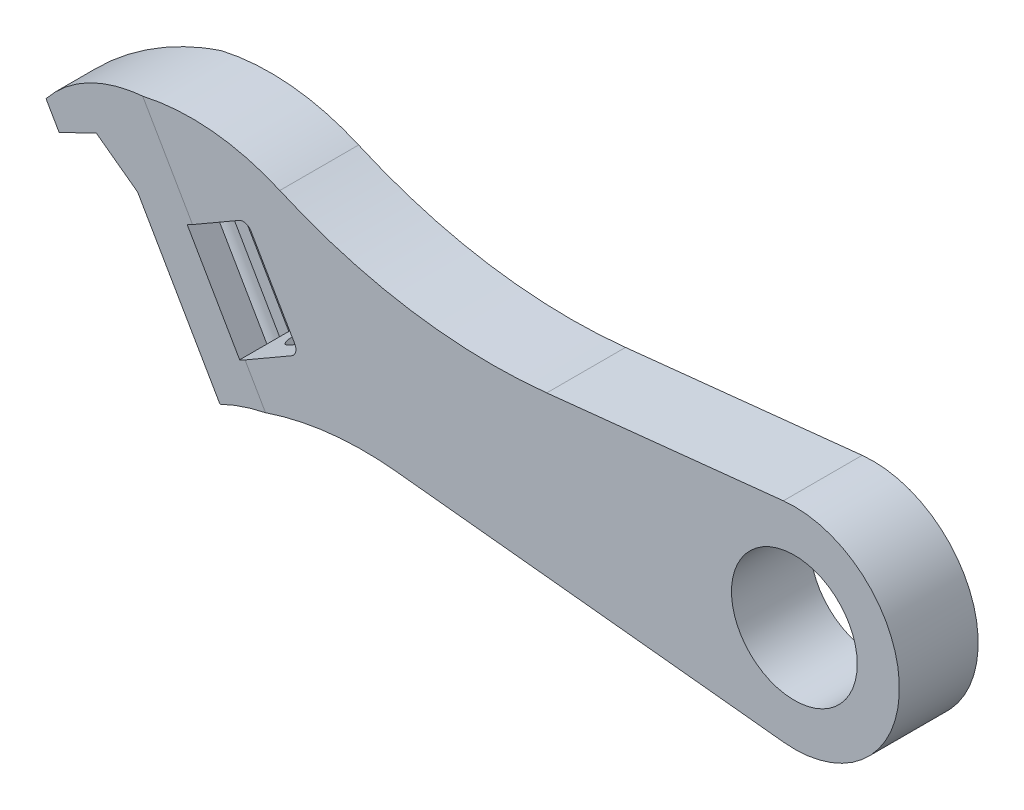
SolidWorks part; units mm, degrees
ref_plane "Front Plane" through (0, 0, 0) normal (0, 0, 1) x (1, 0, 0)
ref_plane "Top Plane" through (0, 0, 0) normal (0, 1, 0) x (1, 0, 0)
ref_plane "Right Plane" through (0, 0, 0) normal (1, 0, 0) x (0, 0, -1)
sketch "Sketch1" plane through (0, 0, 0) normal (0, 0, 1) x (1, 0, 0)
  line L0 (-1.2543, 11.9343) -> (-28.2897, 9.0927)
  line L1 (-1.2543, -11.9343) -> (-45.5473, -7.2789)
  line L2 (0, 0) -> (-132.4095, 0) construction
  line L3 (-88, 7.1064) -> (-86.5, 4.5083)
  line L4 (-86.5, 4.5083) -> (-81.3038, 7.5083)
  line L5 (-81.3038, 7.5083) -> (-76.1077, 4.5083)
  line L6 (-76.1077, 4.5083) -> (-66.7058, -11.7763)
  line L7 (-69.5096, 5.0801) -> (-63.5096, -5.3122)
  line L8 (-63.5096, -5.3122) -> (-57.4474, -1.8122)
  line L9 (-57.0814, -0.4461) -> (-62.0814, 8.2141)
  line L10 (-63.4474, 8.5801) -> (-69.5096, 5.0801)
  line L11 (-95.5176, 16) -> (-42.2419, 16) construction
  line L12 (0, -12) -> (24.4473, -12) construction
  line L13 (-66.7058, -11.7763) -> (-98.6065, -30.1942) construction
  circle A0 centre (0, 0) radius 7.1846
  arc A1 (-1.2543, 11.9343) -> (-1.2543, -11.9343) centre (0, 0) cw
  arc A2 (-45.5473, -7.2789) -> (-66.7058, -11.7763) centre (-49.2058, -42.0872) ccw
  arc A3 (-88, 7.1064) -> (-58.7861, 13.8718) centre (-68.8798, -9) cw
  arc A4 (-28.2897, 9.0927) -> (-58.7861, 13.8718) centre (-34.5614, 68.764) cw
  arc A5 (-57.4474, -1.8122) -> (-57.0814, -0.4461) centre (-57.9474, -0.9461) ccw
  arc A6 (-62.0814, 8.2141) -> (-63.4474, 8.5801) centre (-62.9474, 7.7141) ccw
  point P12 (12, 0)
  point P26 (-62.5814, 9.0801)
  point P30 (-68.8798, 16)
  dimension "D1" = 12
  dimension "D4" = 35
  dimension "D12" = 25
  dimension "D14" = 60
  dimension "D19" = 1
  dimension "D13" = 16
  dimension "D2" = 6
  dimension "D3" = 12
  dimension "D5" = 30
  dimension "D6" = 100
  dimension "D7" = 60
  dimension "D8" = 6
  dimension "D9" = 6
  dimension "D10" = 3
  dimension "D11" = 24
  dimension "D15" = 4
  dimension "D16" = 8
  dimension "D17" = 8
  dimension "D18" = 15
  dimension "D20" = 28
  dimension "D21" = 12
extrude "Boss-Extrude1" add sketch "Sketch1" along normal mid plane 9
sketch "Sketch2" plane through (0, 0, 0) normal (0, 0, 1) x (1, 0, 0)
  line L0 (-75.6836, 24.4558) -> (-54.5156, -12.2084) construction
  line L5 (-63.4474, 8.5801) -> (-69.5096, 5.0801) construction
  line L6 (-81.3038, 7.5083) -> (-69.7502, 14.1788) construction
ref_plane "Plane2" through (-23.5772, 40.8369, 0) normal (0.5, -0.866, 0) x (0.866, 0.5, 0)
sketch "Sketch4" plane through (-23.5772, 40.8369, 0) normal (0.5, -0.866, 0) x (0.866, 0.5, 0)
  line L0 (-66.657, 0) -> (-53.316, 0) construction
  line L1 (-72.657, 4.5) -> (-72.657, -4.5) construction
  line L2 (-57.657, -1.25) -> (-57.657, 1.25)
  line L3 (-57.657, -1.25) -> (-59.0958, -1.25)
  line L4 (-57.657, 1.25) -> (-59.0958, 1.25)
  line L5 (-62.2183, -1.25) -> (-66.657, -1.25)
  line L6 (-62.2183, 1.25) -> (-66.657, 1.25)
  line L7 (-66.657, -1.25) -> (-66.657, 1.25)
  line L8 (-72.657, 4.5) -> (-72.657, 2)
  line L9 (-72.657, 4.5) -> (-72.657, -4.5) construction
  line L10 (-72.657, 2) -> (-56.7908, 4.5)
  line L11 (-56.7908, 4.5) -> (-72.657, 4.5)
  line L12 (55, 0) -> (-55, 0) construction
  line L13 (-72.657, -2) -> (-56.7908, -4.5)
  line L14 (-72.657, -4.5) -> (-72.657, -2)
  line L15 (-56.7908, -4.5) -> (-72.657, -4.5)
  line L17 (-66.657, 4.5) -> (-66.657, -4.5) construction
  circle A0 centre (-53.657, 0) radius 2
  circle A1 centre (-60.657, 0) radius 2
  point P17 (-57.657, 0)
  point P28 (-59.7908, 4.5)
  point P29 (-56.7908, 4.5)
  dimension "D1" = 19
  dimension "D3" = 4
  dimension "D4" = 12
  dimension "D8" = 4
  dimension "D9" = 4
  dimension "D2" = 15
  dimension "D5" = 2.5
  dimension "D6" = 4
  dimension "D7" = 2.5
extrude "Cut-Extrude2" cut sketch "Sketch4" along normal blind 29 from offset 4 contours A0
extrude "Cut-Extrude3" cut sketch "Sketch4<4>" along normal blind 29 contours A1 L6 L7 L5 | A1 | A1 L3 L2 L4 region at (-74.0091, 11.7199, 0) region at (-76.1077, 10.5083, 0) region at (-79.5098, 8.5441, 0)
sketch "Sketch4<4>" plane through (-23.5772, 40.8369, 0) normal (0.5, -0.866, 0) x (0.866, 0.5, 0) same geometry as "Sketch4"
extrude "Cut-Extrude4" cut sketch "Sketch4<6>" along normal blind 29 and the other way blind 29 contours L10 L11 L8 | L15 L13 L14 region at (-81.9198, 7.1527, 3.6667) region at (-81.9198, 7.1527, -3.6667)
sketch "Sketch4<6>" plane through (-23.5772, 40.8369, 0) normal (0.5, -0.866, 0) x (0.866, 0.5, 0) same geometry as "Sketch4"
